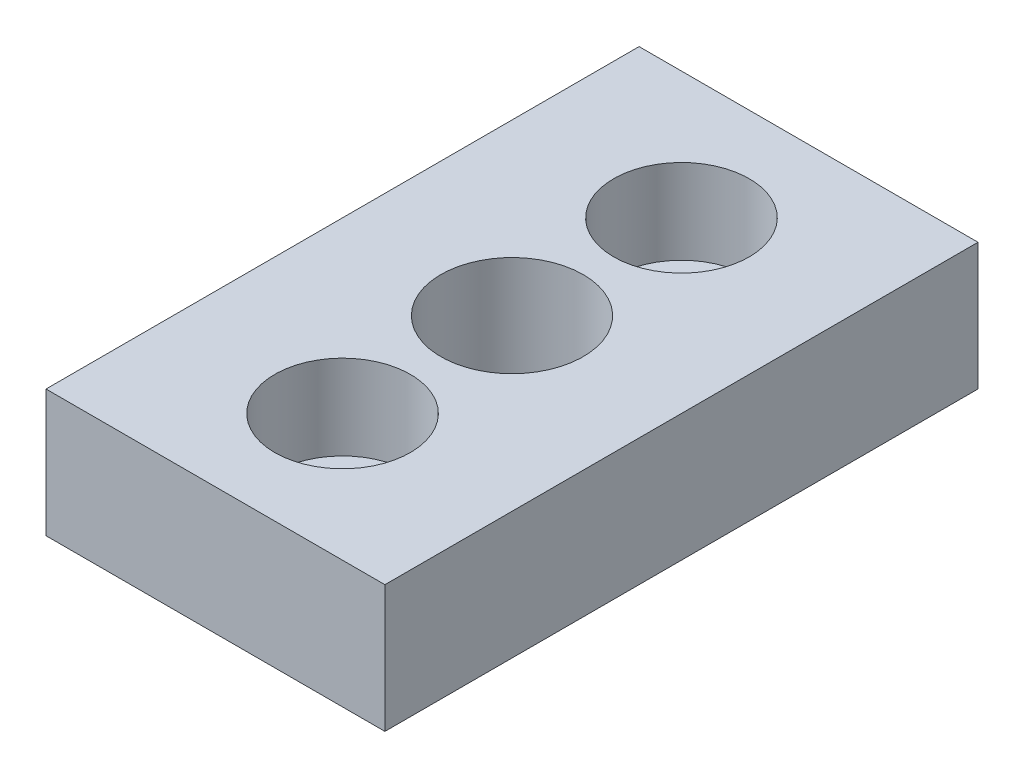
SolidWorks part; units mm, degrees
ref_plane "Front Plane" through (0, 0, 0) normal (0, 0, 1) x (1, 0, 0)
ref_plane "Top Plane" through (0, 0, 0) normal (0, 1, 0) x (1, 0, 0)
ref_plane "Right Plane" through (0, 0, 0) normal (1, 0, 0) x (0, 0, -1)
sketch "Sketch1" plane through (0, 0, 0) normal (0, 1, 0) x (1, 0, 0)
  line L0 (-10, -17.5) -> (-10, 17.5)
  line L1 (-10, -17.5) -> (10, -17.5)
  line L2 (-10, 17.5) -> (10, 17.5)
  line L3 (10, -17.5) -> (10, 17.5)
  line L4 (-10, -17.5) -> (10, 17.5) construction
  line L5 (-10, 17.5) -> (10, -17.5) construction
  point P1 (0, 0)
  dimension "D1" = 35
  dimension "D2" = 20
extrude "Boss-Extrude1" add sketch "Sketch1" along normal blind 7.5 contours L2 L3 L1 L0
sketch "Sketch3" plane through (0, 0, 0) normal (0, -1, 0) x (1, 0, 0)
  circle A0 centre (0, 0) radius 4.2
  dimension "D1" = 8.4
extrude "Cut-Extrude1" cut sketch "Sketch3" against normal through all
sketch "Sketch5" plane through (0, 0, 0) normal (0, -1, 0) x (1, 0, 0)
  line L4 (-10, 17.5) -> (-10, -17.5)
  line L5 (-10, -17.5) -> (10, -17.5)
  line L6 (10, -17.5) -> (10, 17.5)
  line L7 (10, 17.5) -> (-10, 17.5)
  line L8 (-10, 17.5) -> (-10, -17.5)
  line L9 (-10, -17.5) -> (10, -17.5)
  line L10 (10, -17.5) -> (10, 17.5)
  line L11 (10, 17.5) -> (-10, 17.5)
  arc A0 (2.5, 10) -> (1.7678, 8.2322) centre (0, 10) ccw construction
  arc A1 (2.5, -10) -> (1.7678, -11.7678) centre (0, -10) ccw construction
  circle A2 centre (0, 10) radius 2.5
  circle A3 centre (0, -10) radius 2.5
  point P10 (2.5, -10.3172)
  point P12 (2.5, 9.6592)
  dimension "D1" = 0
extrude "Cut-Extrude2" cut sketch "Sketch5" against normal through all contours A3 | A2
sketch "Sketch6" plane through (0, 7.5, 0) normal (0, 1, 0) x (1, 0, 0)
  circle A0 centre (0, 10) radius 4
  circle A1 centre (0, -10) radius 4
  dimension "D1" = 8
  dimension "D2" = 8
extrude "Cut-Extrude3" cut sketch "Sketch6" against normal blind 5
